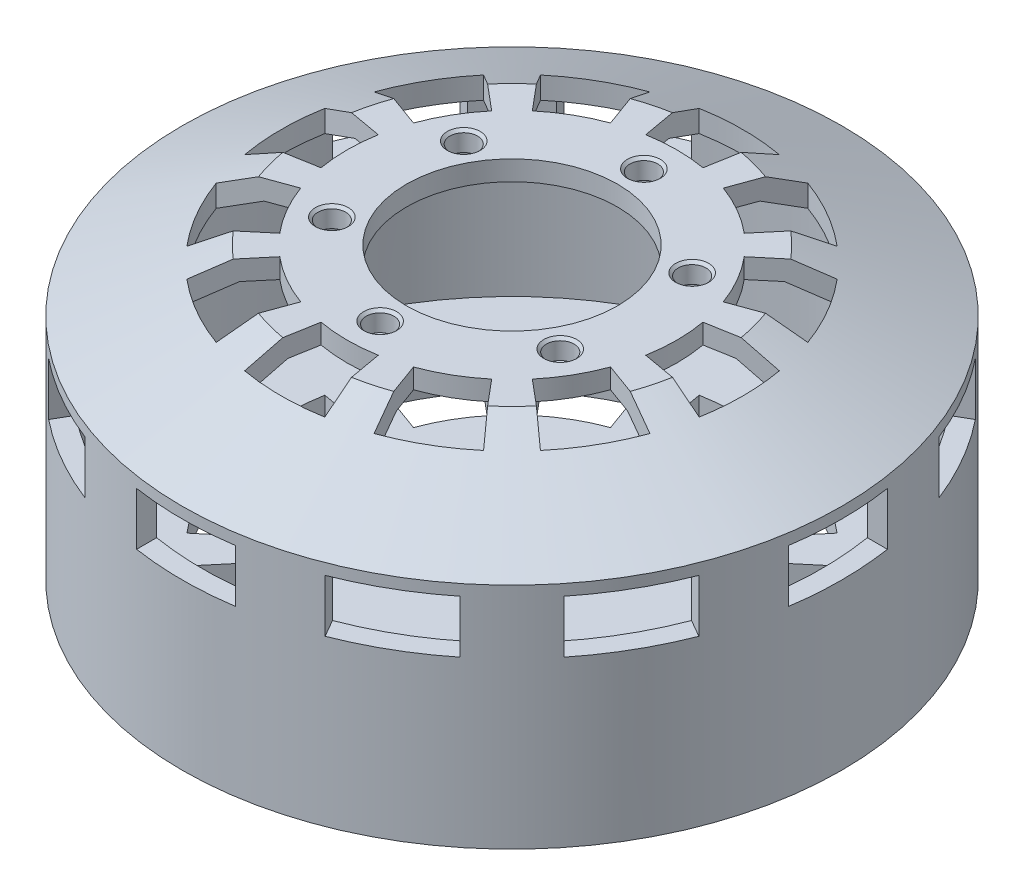
SolidWorks part; units mm, degrees
material "1060 Сплав"
ref_plane "Спереди" through (0, 0, 0) normal (0, 0, 1) x (1, 0, 0)
ref_plane "Сверху" through (0, 0, 0) normal (0, 1, 0) x (1, 0, 0)
ref_plane "Справа" through (0, 0, 0) normal (1, 0, 0) x (0, 0, -1)
other "Configuration Table"
sketch "Эскиз1" plane through (0, 0, 0) normal (0, 1, 0) x (1, 0, 0)
  circle A0 centre (0, 0) radius 50
  dimension "D1" = 100
extrude "Бобышка-Вытянуть1" add sketch "Эскиз1" along normal blind 4
hole_wizard "Сверло под метчик  спиральное M43" positions "Эскиз2" profile "Эскиз3" hole size "M4x0.7" standard "DIN" end condition through all
sketch "Эскиз2" plane through (0, 0, 0) normal (0, -1, 0) x (-1, 0, 0)
  circle A0 centre (0, 0) radius 42.5 construction
  point P5 (0, 42.5)
  point P13 (21.25, 36.8061)
  point P14 (36.8061, 21.25)
  point P15 (42.5, 0)
  point P16 (36.8061, -21.25)
  point P17 (21.25, -36.8061)
  point P19 (21.25, 36.8061)
  point P20 (0, -42.5)
  point P21 (-21.25, -36.8061)
  point P22 (-36.8061, -21.25)
  point P23 (-42.5, 0)
  point P24 (-36.8061, 21.25)
  point P25 (-21.25, 36.8061)
  dimension "D1" = 85
  dimension "D2" = 12
sketch "Эскиз3" plane through (21.25, 0, -36.8061) normal (1, 0, 0) x (0, 0, -1)
  line L0 (0, 0) -> (0, 4)
  line L1 (0, 4) -> (2.1, 4)
  line L2 (2.1, 4) -> (2.1, 0.4)
  line L3 (2.1, 0.4) -> (2.5, 0)
  line L5 (2.5, 0) -> (0, 0)
  line L6 (-2.1, 0.4) -> (-2.5, 0) construction
  line L11 (0, -6.35) -> (0, 107.95) construction
  dimension "Диаметр сквозного отверстия" = 4.2
  dimension "Глубина сквозного отверстия" = 4
  dimension "Диаметр передней зенковки" = 5
  dimension "Угол передней зенковки" = 90
sketch "Эскиз7" plane through (0, 0, 0) normal (0, 0, 1) x (1, 0, 0)
  line L2 (50, 4) -> (50, 34.6738)
  line L3 (50, 34.6738) -> (30, 44)
  line L4 (30, 44) -> (16, 44)
  line L5 (16, 44) -> (16, 41)
  line L6 (16, 41) -> (29.3349, 41)
  line L7 (29.3349, 41) -> (47, 32.7626)
  line L8 (47, 32.7626) -> (47, 4)
  line L9 (0, -1000) -> (0, 49000) construction
  line L10 (50, 4) -> (-50, 4) construction
  line L11 (50, 4) -> (-50, 4) construction
  line L13 (47, 4) -> (50, 4)
  line L14 (-50, 0) -> (50, 0) construction
  dimension "D1" = 3
  dimension "D2" = 3
  dimension "D3" = 3
  dimension "D4" = 44
  dimension "D5" = 60
  dimension "D6" = 25
  dimension "D7" = 32
revolve "Повернуть1" add sketch "Эскиз7" angle 360 about L9 region at (48.5, 4.525, 0)
sketch "Эскиз4" plane through (0, 0, 0) normal (0, -1, 0) x (1, 0, 0)
  line L0 (0, 0) -> (0, 35) construction
  line L1 (-6.0777, 34.4683) -> (-4.3412, 24.6202)
  line L2 (6.0777, 34.4683) -> (4.3412, 24.6202)
  line L3 (11.9707, 32.8892) -> (8.5505, 23.4923)
  line L4 (22.4976, 26.8116) -> (16.0697, 19.1511)
  line L5 (0, 0) -> (17.5, 30.3109) construction
  line L6 (26.8116, 22.4976) -> (19.1511, 16.0697)
  line L7 (32.8892, 11.9707) -> (23.4923, 8.5505)
  line L8 (0, 0) -> (30.3109, 17.5) construction
  line L9 (34.4683, 6.0777) -> (24.6202, 4.3412)
  line L10 (34.4683, -6.0777) -> (24.6202, -4.3412)
  line L11 (0, 0) -> (35, 0) construction
  line L12 (32.8892, -11.9707) -> (23.4923, -8.5505)
  line L13 (26.8116, -22.4976) -> (19.1511, -16.0697)
  line L14 (0, 0) -> (30.3109, -17.5) construction
  line L15 (22.4976, -26.8116) -> (16.0697, -19.1511)
  line L16 (11.9707, -32.8892) -> (8.5505, -23.4923)
  line L17 (0, 0) -> (17.5, -30.3109) construction
  line L18 (6.0777, -34.4683) -> (4.3412, -24.6202)
  line L19 (-6.0777, -34.4683) -> (-4.3412, -24.6202)
  line L20 (0, 0) -> (0, -35) construction
  line L21 (-11.9707, -32.8892) -> (-8.5505, -23.4923)
  line L22 (-22.4976, -26.8116) -> (-16.0697, -19.1511)
  line L23 (0, 0) -> (-17.5, -30.3109) construction
  line L24 (-26.8116, -22.4976) -> (-19.1511, -16.0697)
  line L25 (-32.8892, -11.9707) -> (-23.4923, -8.5505)
  line L26 (0, 0) -> (-30.3109, -17.5) construction
  line L27 (-34.4683, -6.0777) -> (-24.6202, -4.3412)
  line L28 (-34.4683, 6.0777) -> (-24.6202, 4.3412)
  line L29 (0, 0) -> (-35, 0) construction
  line L30 (-32.8892, 11.9707) -> (-23.4923, 8.5505)
  line L31 (-26.8116, 22.4976) -> (-19.1511, 16.0697)
  line L32 (0, 0) -> (-30.3109, 17.5) construction
  line L33 (-22.4976, 26.8116) -> (-16.0697, 19.1511)
  line L34 (-11.9707, 32.8892) -> (-8.5505, 23.4923)
  line L35 (0, 0) -> (-17.5, 30.3109) construction
  arc A0 (6.0777, 34.4683) -> (-6.0777, 34.4683) centre (0, 0) ccw
  arc A1 (4.3412, 24.6202) -> (-4.3412, 24.6202) centre (0, 0) ccw
  arc A2 (22.4976, 26.8116) -> (11.9707, 32.8892) centre (0, 0) ccw
  arc A3 (16.0697, 19.1511) -> (8.5505, 23.4923) centre (0, 0) ccw
  arc A4 (32.8892, 11.9707) -> (26.8116, 22.4976) centre (0, 0) ccw
  arc A5 (23.4923, 8.5505) -> (19.1511, 16.0697) centre (0, 0) ccw
  arc A6 (34.4683, -6.0777) -> (34.4683, 6.0777) centre (0, 0) ccw
  arc A7 (24.6202, -4.3412) -> (24.6202, 4.3412) centre (0, 0) ccw
  arc A8 (26.8116, -22.4976) -> (32.8892, -11.9707) centre (0, 0) ccw
  arc A9 (19.1511, -16.0697) -> (23.4923, -8.5505) centre (0, 0) ccw
  arc A10 (11.9707, -32.8892) -> (22.4976, -26.8116) centre (0, 0) ccw
  arc A11 (8.5505, -23.4923) -> (16.0697, -19.1511) centre (0, 0) ccw
  arc A12 (-6.0777, -34.4683) -> (6.0777, -34.4683) centre (0, 0) ccw
  arc A13 (-4.3412, -24.6202) -> (4.3412, -24.6202) centre (0, 0) ccw
  arc A14 (-22.4976, -26.8116) -> (-11.9707, -32.8892) centre (0, 0) ccw
  arc A15 (-16.0697, -19.1511) -> (-8.5505, -23.4923) centre (0, 0) ccw
  arc A16 (-32.8892, -11.9707) -> (-26.8116, -22.4976) centre (0, 0) ccw
  arc A17 (-23.4923, -8.5505) -> (-19.1511, -16.0697) centre (0, 0) ccw
  arc A18 (-34.4683, 6.0777) -> (-34.4683, -6.0777) centre (0, 0) ccw
  arc A19 (-24.6202, 4.3412) -> (-24.6202, -4.3412) centre (0, 0) ccw
  arc A20 (-26.8116, 22.4976) -> (-32.8892, 11.9707) centre (0, 0) ccw
  arc A21 (-19.1511, 16.0697) -> (-23.4923, 8.5505) centre (0, 0) ccw
  arc A22 (-11.9707, 32.8892) -> (-22.4976, 26.8116) centre (0, 0) ccw
  arc A23 (-8.5505, 23.4923) -> (-16.0697, 19.1511) centre (0, 0) ccw
  point P65 (0, 0)
  dimension "D1" = 35
  dimension "D2" = 25
  dimension "D3" = 20
  dimension "D4" = 12
extrude "Вырез-Вытянуть1" cut sketch "Эскиз4" against normal through all
sketch "Эскиз11" plane through (0, 0, 0) normal (1, 0, 0) x (0, 0, -1)
  line L0 (0, -1000) -> (0, 49000) construction
  line L2 (-7.5, 25) -> (7.5, 25)
  line L3 (-7.5, 25) -> (-7.5, 33)
  line L4 (-7.5, 33) -> (7.5, 33)
  line L5 (7.5, 25) -> (7.5, 33)
  line L6 (-7.5, 25) -> (7.5, 33) construction
  line L7 (-7.5, 33) -> (7.5, 25) construction
  point P1 (0, 29)
  dimension "D1" = 15
  dimension "D2" = 8
  dimension "D3" = 25
extrude "Вырез-Вытянуть2" cut sketch "Эскиз11" against normal through all
pattern_circular "Круговой массив1" count 12 over 360 about axis through (0, -1000, 0) along (0, 1, 0) of "Вырез-Вытянуть2"
hole_wizard "Сверло под метчик  спиральное M44" positions "Эскиз13" profile "Эскиз14" hole size "M4x0.7" standard "DIN" end condition up to next
sketch "Эскиз13" plane through (0, 44, 0) normal (0, 1, 0) x (1, 0, 0)
  line L0 (0, 0) -> (0, 20) construction
  circle A0 centre (0, 0) radius 20 construction
  point P5 (0, 20)
  point P12 (17.3205, 10)
  point P13 (17.3205, -10)
  point P14 (0, -20)
  point P15 (-17.3205, -10)
  point P16 (-17.3205, 10)
  point P19 (0, 0)
  dimension "D1" = 40
  dimension "D3" = 20
  dimension "D2" = 6
sketch "Эскиз14" plane through (-17.3205, 44, -10) normal (1, 0, 0) x (0, 0, 1)
  line L0 (0, 0) -> (0, 3)
  line L1 (0, 3) -> (2.1, 3)
  line L2 (2.1, 3) -> (2.1, 0.4)
  line L3 (2.1, 0.4) -> (2.5, 0)
  line L5 (2.5, 0) -> (0, 0)
  line L6 (-2.1, 0.4) -> (-2.5, 0) construction
  line L11 (0, -6.35) -> (0, 107.95) construction
  dimension "Диаметр сквозного отверстия" = 4.2
  dimension "Глубина сквозного отверстия" = 3
  dimension "Диаметр передней зенковки" = 5
  dimension "Угол передней зенковки" = 90
